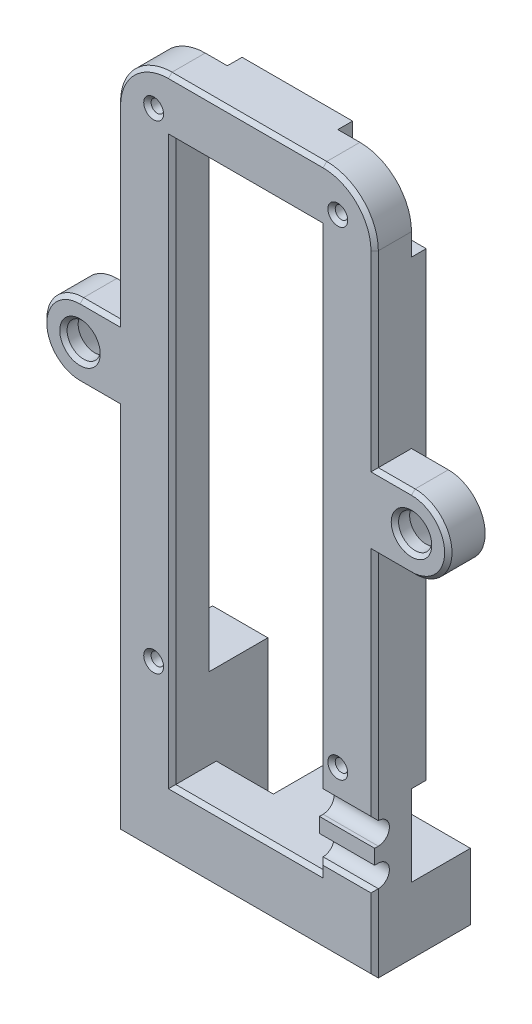
SolidWorks part; units mm, degrees
ref_plane "Front Plane" through (0, 0, 0) normal (0, 0, 1) x (1, 0, 0)
ref_plane "Top Plane" through (0, 0, 0) normal (0, 1, 0) x (1, 0, 0)
ref_plane "Right Plane" through (0, 0, 0) normal (1, 0, 0) x (0, 0, -1)
sketch "Sketch1" plane through (0, 0, 0) normal (0, 0, 1) x (1, 0, 0)
  line L0 (-10, -35) -> (-10, 30)
  line L1 (-15, -35) -> (15, -35) construction
  line L2 (-15, -35) -> (-15, 35) construction
  line L3 (-15, 35) -> (15, 35) construction
  line L4 (15, -35) -> (15, 35) construction
  line L5 (-10, 30) -> (10, 30)
  line L6 (10, 30) -> (10, -35)
  line L7 (-10, -35) -> (-17.5, -35)
  line L8 (-17.5, -35) -> (-17.5, 37.5)
  line L9 (-17.5, 37.5) -> (17.5, 37.5)
  line L10 (17.5, 37.5) -> (17.5, -35)
  line L11 (17.5, -35) -> (10, -35)
  circle A0 centre (-12.5, 32.5) radius 0.85
  circle A1 centre (12.5, 32.5) radius 0.85
  circle A2 centre (-12.5, -32.5) radius 0.85
  circle A3 centre (12.5, -32.5) radius 0.85
  point P4 (0, 35)
  point P5 (-15, 0)
  point P21 (0, 0)
  point P22 (0, 0)
  point P23 (0, 0)
  point P26 (0, 0)
  point P27 (0, 0)
  dimension "D6" = 1.7
  dimension "D14" = 2.5
  dimension "D1" = 30
  dimension "D2" = 70
  dimension "D3" = 5
  dimension "D4" = 5
  dimension "D5" = 5
  dimension "D7" = 2.5
  dimension "D8" = 2.5
  dimension "D9" = 2.5
  dimension "D10" = 2.5
  dimension "D11" = 7.5
  dimension "D12" = 7.5
  dimension "D13" = 7.5
  dimension "D15" = 2.5
  dimension "D16" = 2.5
extrude "Boss-Extrude1" add sketch "Sketch1" along normal blind 5
sketch "Sketch2" plane through (0, 0, 0) normal (0, 0, 1) x (1, 0, 0)
  line L0 (17.5, -35) -> (10, -35) construction
  line L1 (17.5, 37.5) -> (30, 37.5)
  line L2 (17.5, 37.5) -> (17.5, -35)
  line L3 (17.5, -35) -> (15.1, -35)
  line L4 (15.1, 35.1) -> (15.1, -35)
  line L5 (-17.5, 37.5) -> (-30, 37.5)
  line L6 (-17.5, 37.5) -> (-17.5, -35)
  line L7 (-17.5, -35) -> (-15.1, -35)
  line L8 (-15.1, 35.1) -> (-15.1, -35)
  line L9 (30, 37.5) -> (-30, 37.5)
  line L11 (15.1, 35.1) -> (-15.1, 35.1)
  line L12 (15, -35) -> (15, 35) construction
  line L13 (-17.5, -35) -> (-10, -35) construction
  line L15 (-15, -35) -> (-15, 35) construction
  line L16 (-15, 35) -> (15, 35) construction
  dimension "D1" = 0.1
  dimension "D2" = 0.1
  dimension "D3" = 0.1
extrude "Boss-Extrude2" add sketch "Sketch2" against normal blind 2 contours L11 L4 L3 L2 L9 L6 L7 L8
sketch "Sketch3" plane through (0, 0, 0) normal (0, 0, 1) x (1, 0, 0)
  line L0 (17.5, 37.5) -> (17.5, -35) construction
  line L1 (22.5, 5) -> (17.5, 5)
  line L3 (22.5, -5) -> (17.5, -5)
  line L4 (17.5, 5) -> (17.5, -5)
  line L5 (-17.5, -35) -> (-17.5, 37.5) construction
  line L6 (-22.5, 5) -> (-17.5, 5)
  line L8 (-22.5, -5) -> (-17.5, -5)
  line L9 (-17.5, 5) -> (-17.5, -5)
  arc A0 (22.5, -5) -> (22.5, 5) centre (22.5, 0) ccw
  arc A1 (-22.5, 5) -> (-22.5, -5) centre (-22.5, 0) ccw
  circle A2 centre (22.5, 0) radius 2.25
  circle A3 centre (-22.5, 0) radius 2.25
  dimension "D1" = 10
  dimension "D2" = 10
  dimension "D3" = 4.5
  dimension "D4" = 4.5
extrude "Boss-Extrude3" add sketch "Sketch3" along normal up to surface (5 mm away) up to face at (0, -0.625, 5)
sketch "Sketch4" plane through (0, 0, 0) normal (0, 0, -1) x (-1, 0, 0)
  circle A0 centre (-22.5, 0) radius 3.5
  circle A1 centre (22.5, 0) radius 3.5
  dimension "D1" = 7
  dimension "D2" = 7
extrude "Cut-Extrude1" cut sketch "Sketch4" against normal blind 3
sketch "Sketch5" plane through (0, 0, 0) normal (0, 0, -1) x (-1, 0, 0)
  line L1 (-7.5, 37.5) -> (-17.5, 37.5)
  line L2 (-7.5, 37.5) -> (-7.5, 27.5)
  line L3 (-7.5, 27.5) -> (-17.5, 27.5)
  line L4 (-17.5, 37.5) -> (-17.5, 27.5)
  line L5 (-7.5, 37.5) -> (-17.5, 27.5) construction
  line L6 (-7.5, 27.5) -> (-17.5, 37.5) construction
  line L7 (7.5, 37.5) -> (17.5, 37.5)
  line L8 (7.5, 37.5) -> (7.5, 27.5)
  line L9 (7.5, 27.5) -> (17.5, 27.5)
  line L10 (17.5, 37.5) -> (17.5, 27.5)
  line L11 (7.5, 37.5) -> (17.5, 27.5) construction
  line L12 (7.5, 27.5) -> (17.5, 37.5) construction
  point P0 (-12.5, 32.5)
  point P5 (12.5, 32.5)
  point P12 (0, 0)
  point P13 (0, 0)
  point P17 (20.8445, 36.306)
extrude "Cut-Extrude2" cut sketch "Sketch5" along normal through all
fillet "Fillet1" radius 7 2 edges at (-17.5, 37.5, 2.5) (17.5, 37.5, 2.5)
sketch "Sketch6" plane through (0, 0, 0) normal (0, 0, 1) x (1, 0, 0)
  line L1 (-17.5, -35) -> (-10, -35)
  line L2 (-17.5, -35) -> (-17.5, -55)
  line L3 (-17.5, -55) -> (-10, -55)
  line L4 (-10, -35) -> (-10, -55)
  line L5 (-10, -35) -> (-10, 30) construction
  dimension "D1" = 20
extrude "Boss-Extrude4" add sketch "Sketch6" along normal up to surface (5 mm away) and the other way blind 8 up to face at (0, 3.2722, 5)
sketch "Sketch7" plane through (-10, 0, 0) normal (1, 0, 0) x (0, 0, -1)
  line L0 (8, -35) -> (0, -35) construction
  line L1 (-5, -55) -> (1, -55)
  line L2 (-5, -55) -> (-5, -46)
  line L3 (-5, -46) -> (1, -46)
  line L4 (1, -55) -> (1, -46)
  line L5 (0, -35) -> (0, 30) construction
  dimension "D1" = 11
  dimension "D2" = 1
extrude "Boss-Extrude5" add sketch "Sketch7" along normal up to surface (27.5 mm away) up to face at (17.5, 4.6, 1.6)
sketch "Sketch8" plane through (0, 0, -1) normal (0, 0, -1) x (-1, 0, 0)
  line L1 (-17.5, -46) -> (2.25, -46)
  line L2 (-17.5, -46) -> (-17.5, -55)
  line L3 (-17.5, -55) -> (2.25, -55)
  line L4 (2.25, -46) -> (2.25, -55)
  line L5 (-17.5, -55) -> (10, -55) construction
  line L6 (10, -55) -> (10, -46) construction
  point P4 (0.8797, -60)
  point P7 (0, 0)
  dimension "D1" = 7.75
extrude "Boss-Extrude6" add sketch "Sketch8" along normal up to surface (7 mm away) up to face at (-13.75, -45, -8)
sketch "Sketch9" plane through (0, -35, 0) normal (0, -1, 0) x (1, 0, 0)
  line L1 (10, 0) -> (17.5, 0)
  line L2 (10, 0) -> (10, 5)
  line L3 (10, 5) -> (17.5, 5)
  line L4 (17.5, 0) -> (17.5, 5)
extrude "Boss-Extrude7" add sketch "Sketch9" along normal up to surface (11 mm away) up to face at (1.75, -46, -1.3333)
sketch "Sketch10" plane through (17.5, 0, 0) normal (1, 0, 0) x (0, 0, -1)
  line L0 (0, -35) -> (-5, -35) construction
  line L1 (-5, -55) -> (-5, -5) construction
  line L2 (0, -46) -> (-5, -46) construction
  line L3 (-4.5, -36.5) -> (-6, -36.5)
  line L4 (-6, -36.5) -> (-6, -44.5)
  line L5 (-6, -44.5) -> (-4.5, -44.5)
  line L6 (-4.5, -39.5) -> (-5, -39.5)
  line L7 (-5, -39.5) -> (-5, -41.5)
  line L8 (-5, -41.5) -> (-4.5, -41.5)
  arc A0 (-4.5, -39.5) -> (-4.5, -36.5) centre (-4.5, -38) ccw
  arc A1 (-4.5, -44.5) -> (-4.5, -41.5) centre (-4.5, -43) ccw
  arc A2 (-6, -38) -> (-4.5, -39.5) centre (-4.5, -38) ccw construction
  arc A3 (-4.5, -41.5) -> (-6, -43) centre (-4.5, -43) ccw construction
  arc A4 (-6, -43) -> (-4.5, -44.5) centre (-4.5, -43) ccw construction
  arc A5 (-4.5, -36.5) -> (-6, -38) centre (-4.5, -38) ccw construction
  point P20 (-5, -41.5)
  dimension "D1" = 3
  dimension "D2" = 3
  dimension "D3" = 5
  dimension "D4" = 3
  dimension "D5" = 0.5
extrude "Cut-Extrude3" cut sketch "Sketch10" against normal up to surface (7.5 mm away) up to face at (10, -8, 2.5)
chamfer "Chamfer3" distance 0.5 angle 45 36 edges at (0, 30, 5) (-17.5, 17.75, 5) (0, 37.5, 5) (15.4497, 35.4497, 5) (-15.4497, 35.4497, 5) (10, -3.25, 5) (0, -55, 5) (-10, -8, 5) (0, -46, 5) (-11.65, 32.5, 0) (-11.65, 32.5, 5) (10, -45.25, 5) (10, -36.5, 4.75) (17.5, -20.75, 5) (17.5, -36.5, 4.75) (17.5, -44.5, 4.75) (10, -44.5, 4.75) (13.75, -44.5, 5) (13.75, -36.5, 5) (17.5, -49.75, 5) (13.35, 32.5, 0) (13.35, 32.5, 5) (-11.65, -32.5, 0) (-11.65, -32.5, 5) (13.35, -32.5, 0) (13.35, -32.5, 5) (17.5, 17.75, 5) (27.5, 0, 5) (20, 5, 5) (20, -5, 5) (20.25, 0, 5) (-17.5, -30, 5) (-27.5, 0, 5) (-20, -5, 5) (-20, 5, 5) (-24.75, 0, 5)
chamfer "Chamfer1" distance 2.5 distance2 1.25 2 edges at (-26, 0, 3) (19, 0, 3)
